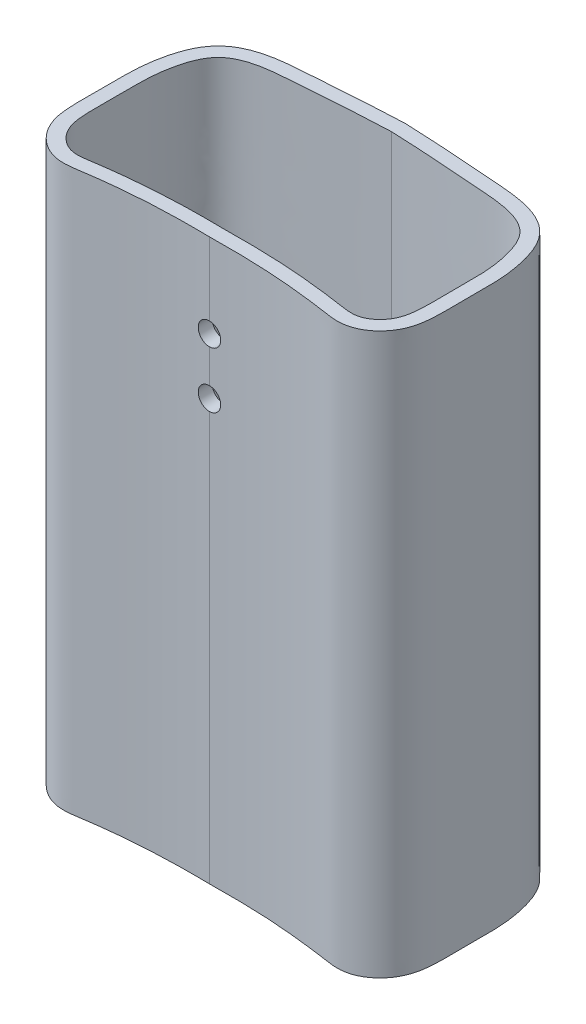
SolidWorks part; units mm, degrees
ref_plane "Ön Düzlem" through (0, 0, 0) normal (0, 0, 1) x (1, 0, 0)
ref_plane "Üst Düzlem" through (0, 0, 0) normal (0, 1, 0) x (1, 0, 0)
ref_plane "Sağ Düzlem" through (0, 0, 0) normal (1, 0, 0) x (0, 0, -1)
sketch "Çizim1" plane through (0, 0, 0) normal (0, 1, 0) x (1, 0, 0)
  line L0 (0, 17.9288) -> (0, -12.0712) construction
  line L1 (0, 0) -> (-30, 0) construction
  line L2 (-108.3091, -42.1463) -> (-63.9653, -42.1463) construction
  spline S0 degree 3 poles (0, 17.9288) (-5.8202, 17.7095) (-13.9034, 17.0426) (-26.8757, 16.196) (-29.5503, 8.9293) (-30.0905, 4.3361) (-29.9407, -0.8874) (-30.1549, -5.7017) (-29.6372, -10.9288) (-26.0312, -14.0818) (-15.7201, -12.3493) (-7.8072, -11.9389) (0, -12.0712) knots 0 0 0 0 0.19846 0.336013 0.394477 0.45973 0.505377 0.582751 0.635933 0.690009 0.731881 1 1 1 1
  spline S1 degree 3 poles (0, 17.9288) (5.8202, 17.7095) (13.9034, 17.0426) (26.8757, 16.196) (29.5503, 8.9293) (30.0905, 4.3361) (29.9407, -0.8874) (30.1549, -5.7017) (29.6372, -10.9288) (26.0312, -14.0818) (15.7201, -12.3493) (7.8072, -11.9389) (0, -12.0712) knots 0 0 0 0 0.19846 0.336013 0.394477 0.45973 0.505377 0.582751 0.635933 0.690009 0.731881 1 1 1 1
  spline S2 degree 1 poles (0, 20.4306) (0, -14.5715) knots 0 0 1 1 construction
  spline S3 degree 1 poles (0, 20.4306) (0, -14.5715) knots 0 0 1 1 construction
  spline S4 degree 3 poles (0, 20.4306) (-0.458, 20.4134) (-1.3822, 20.3764) (-3.165, 20.2946) (-5.3302, 20.178) (-7.8603, 20.0196) (-10.3732, 19.846) (-12.9182, 19.6624) (-15.5373, 19.4674) (-18.3086, 19.2842) (-21.32, 18.9837) (-24.3573, 18.3421) (-26.8186, 17.2691) (-28.5927, 15.8928) (-30.1204, 14.0979) (-31.251, 11.5968) (-32.0035, 8.6964) (-32.4214, 5.8792) (-32.5443, 3.061) (-32.4883, 0.4255) (-32.5154, -2.0532) (-32.5506, -4.2601) (-32.5202, -6.0784) (-32.4358, -7.9603) (-32.1404, -10.1403) (-31.0544, -12.425) (-29.866, -13.91) (-28.3793, -15.1234) (-26.8763, -15.8415) (-25.5259, -16.133) (-24.2777, -16.2204) (-22.882, -16.0982) (-21.5401, -15.8778) (-20.2772, -15.6955) (-19.0082, -15.5229) (-17.3347, -15.3151) (-15.2591, -15.0918) (-12.7819, -14.8803) (-9.4746, -14.6692) (-6.1223, -14.559) (-2.6789, -14.5381) (-0.887, -14.5565) (0, -14.5715) knots -0.00107 -0.00107 -0.00107 -0.00107 0.014579 0.030229 0.061527 0.092826 0.124124 0.155423 0.186722 0.21802 0.249319 0.280617 0.311916 0.327565 0.343215 0.374513 0.405812 0.43711 0.468409 0.499707 0.531006 0.562305 0.577954 0.593603 0.624902 0.640551 0.6562 0.67185 0.687499 0.695324 0.703148 0.718798 0.734447 0.750096 0.765745 0.781395 0.812693 0.843992 0.87529 0.937888 0.969186 1.000485 1.000485 1.000485 1.000485
  spline S5 degree 3 poles (0, -14.5715) (0.887, -14.5565) (2.6789, -14.5381) (6.1223, -14.559) (9.4746, -14.6692) (12.7819, -14.8803) (15.2591, -15.0918) (17.3347, -15.3151) (19.0082, -15.5229) (20.2772, -15.6955) (21.5401, -15.8778) (22.882, -16.0982) (24.2777, -16.2204) (25.5259, -16.133) (26.8763, -15.8415) (28.3793, -15.1234) (29.866, -13.91) (31.0544, -12.425) (32.1404, -10.1403) (32.4358, -7.9603) (32.5202, -6.0784) (32.5506, -4.2601) (32.5154, -2.0532) (32.4883, 0.4255) (32.5443, 3.061) (32.4214, 5.8792) (32.0035, 8.6964) (31.251, 11.5968) (30.1204, 14.0979) (28.5927, 15.8928) (26.8186, 17.2691) (24.3573, 18.3421) (21.32, 18.9837) (18.3086, 19.2842) (15.5373, 19.4674) (12.9182, 19.6624) (10.3732, 19.846) (7.8603, 20.0196) (5.3302, 20.178) (3.165, 20.2946) (1.3822, 20.3764) (0.458, 20.4134) (0, 20.4306) knots -0.00107 -0.00107 -0.00107 -0.00107 0.030229 0.061527 0.124124 0.155423 0.186722 0.21802 0.233669 0.249319 0.264968 0.280617 0.296267 0.304091 0.311916 0.327565 0.343215 0.358864 0.374513 0.405812 0.421461 0.43711 0.468409 0.499707 0.531006 0.562305 0.593603 0.624902 0.6562 0.67185 0.687499 0.718798 0.750096 0.781395 0.812693 0.843992 0.87529 0.906589 0.937888 0.969186 0.984836 1.000485 1.000485 1.000485 1.000485
  dimension "D1" = 30
  dimension "D2" = 30
  dimension "D3" = 2.5
extrude "Yükseklik-Ekstrüzyon1" add sketch "Çizim1" along normal blind 100
sketch "Çizim2" plane through (0, 100, 0) normal (0, 1, 0) x (1, 0, 0)
  line L0 (0, -14.5715) -> (0, -12.0712)
ref_plane "Düzlem1" through (0, 0, 14.5715) normal (0, 0, -1) x (-1, 0, 0)
sketch "Çizim3" plane through (0, 0, 14.5715) normal (0, 0, -1) x (-1, 0, 0)
  line L0 (0, 100) -> (0, 0) construction
  circle A0 centre (0, 85) radius 2
  circle A1 centre (0, 75) radius 2
  dimension "D1" = 10
  dimension "D2" = 15
extrude "Kes-Ekstrüzyon1" cut sketch "Çizim3" along normal blind 10
